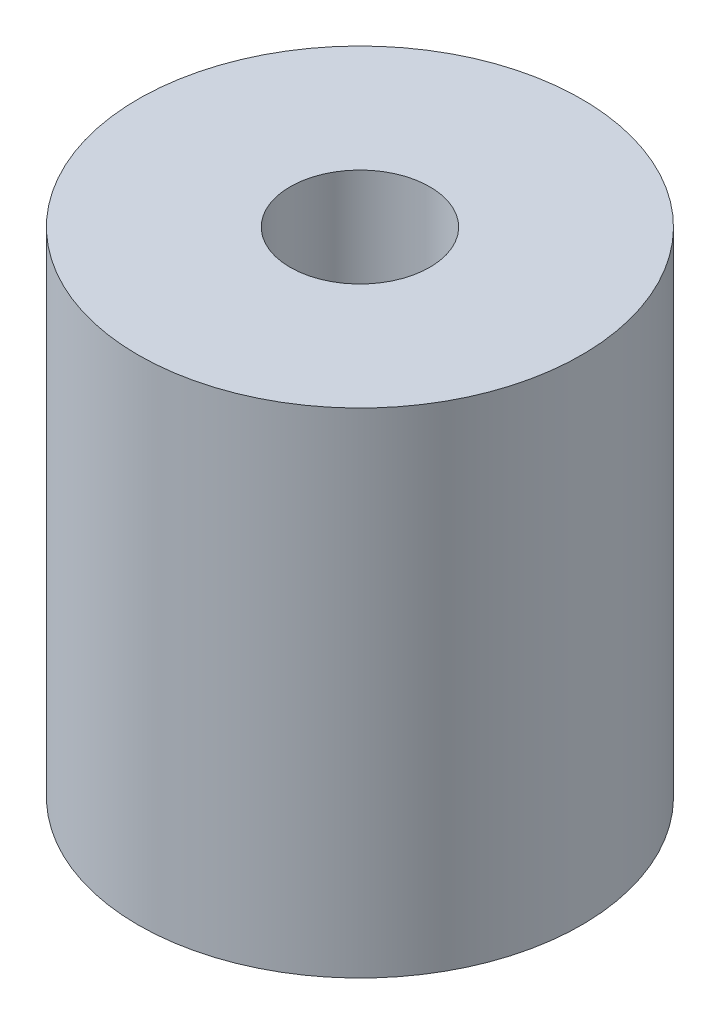
SolidWorks part; units mm, degrees
ref_plane "Front Plane" through (0, 0, 0) normal (0, 0, 1) x (1, 0, 0)
ref_plane "Top Plane" through (0, 0, 0) normal (0, 1, 0) x (1, 0, 0)
ref_plane "Right Plane" through (0, 0, 0) normal (1, 0, 0) x (0, 0, -1)
sketch "Sketch1" plane through (0, 0, 0) normal (0, 1, 0) x (1, 0, 0)
  circle A0 centre (0, 0) radius 5
  circle A1 centre (0, 0) radius 1.575
  dimension "D1" = 10
  dimension "D2" = 3.15
extrude "Boss-Extrude1" add sketch "Sketch1" along normal blind 11.132
sketch "Sketch2" plane through (0, 11.132, 0) normal (0, 1, 0) x (1, 0, 0)
  circle A0 centre (0, 0) radius 1.925
  dimension "D1" = 3.85
extrude "Cut-Extrude1" [suppressed] cut sketch "Sketch2" against normal blind 4
equation "\"D1@Boss-Extrude1\"=\"sheetThickness\"*2+0.5*\"ballBearDiam\""
equation "\"largeBearOD\"= 21mm"
equation "\"largeBearID\"= 15mm"
equation "\"largeBearOTight\"= 0.127mm'calibrate - hold onto gears"
equation "\"largeBearITight\"= 0mm'calibrate - hold onto eccentric nut"
equation "\"largeBearFlangeDiam\"= 22.5mm"
equation "\"largeBearFlangeWidth\"= 0.8mm"
equation "\"smallBearOD\"= 15mm"
equation "\"smallBearOTight\"= 0mm'calibrate - hold onto bottom of gearbox"
equation "\"smallBearOLoose\"= 0mm'calibrate - able to take off topHat"
equation "\"smallBearID\"= 10mm"
equation "\"smallBearITight\"= 0mm'hold onto "
equation "\"pinCircleDiam\"= 75mm"
equation "\"pinDiam\"= 6mm"
equation "\"sheetThickness\"= 0.1875in"
equation "\"ballBearDiam\"= 3.214mm"
equation "\"thrustBearingThickness\"= 5mm'measure this irl and change"
equation "\"thrustBearingID\"= 0mm'measure this irl and change"
equation "\"thrustBearingOD\"= 0mm'measure this irl and change"
equation "\"eccentricity\"= 1mm"
